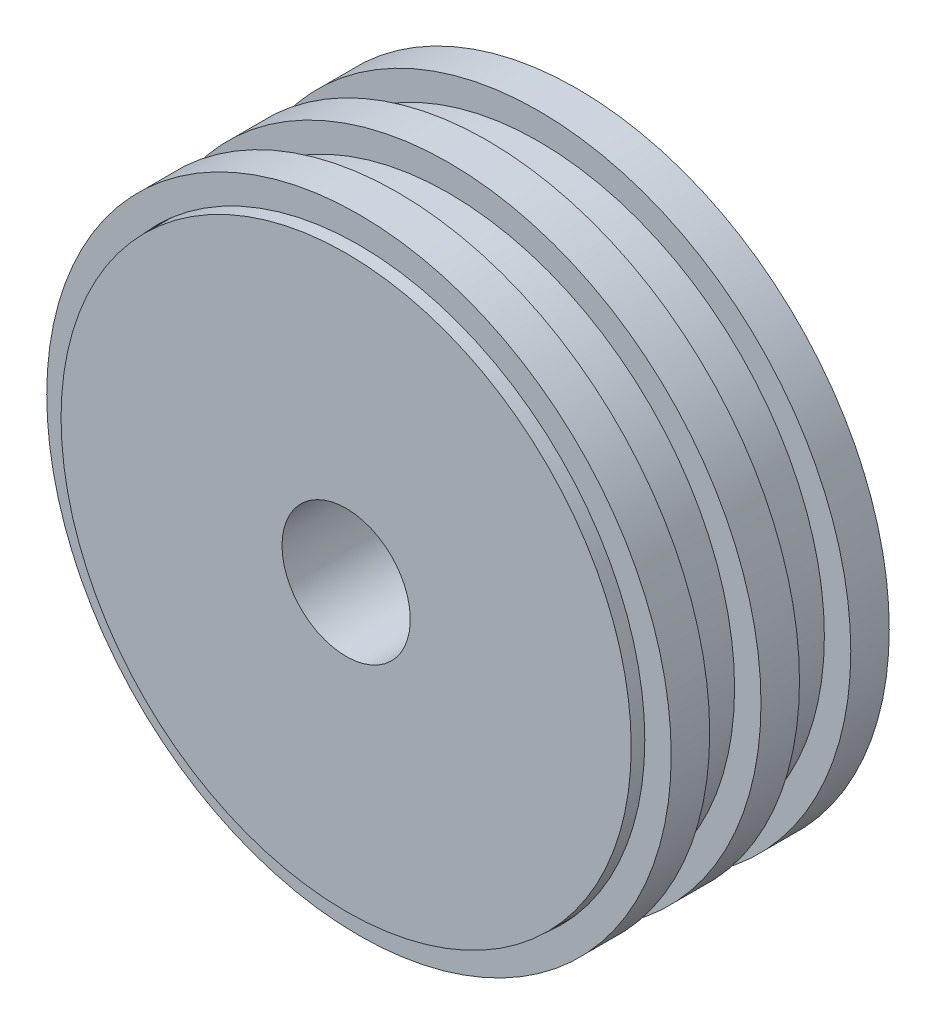
SolidWorks part; units mm, degrees
ref_plane "Front Plane" through (0, 0, 0) normal (0, 0, 1) x (1, 0, 0)
ref_plane "Top Plane" through (0, 0, 0) normal (0, 1, 0) x (1, 0, 0)
ref_plane "Right Plane" through (0, 0, 0) normal (1, 0, 0) x (0, 0, -1)
sketch "Sketch1" plane through (0, 0, 0) normal (0, 0, 1) x (1, 0, 0)
  circle A0 centre (0, 0) radius 66.675
  circle A1 centre (0, 0) radius 15
  dimension "D1" = 133.35
  dimension "D2" = 30
extrude "Boss-Extrude1" add sketch "Sketch1" along normal blind 57
ref_plane "Plane1" through (0, 0, 54) normal (0, 0, 1) x (1, 0, 0)
sketch "Sketch2" plane through (0, 0, 54) normal (0, 0, 1) x (1, 0, 0)
  circle A0 centre (0, 0) radius 73.025
  circle A1 centre (0, 0) radius 66.8499
  dimension "D1" = 146.05
extrude "Boss-Extrude2" add sketch "Sketch2" against normal blind 9 separate body
ref_axis "Axis1" through (0, 0, 57) along (0, 0, -1)
pattern_linear "LPattern1" count 3 spacing 21 along (0, 0, -1) of "Boss-Extrude2"
